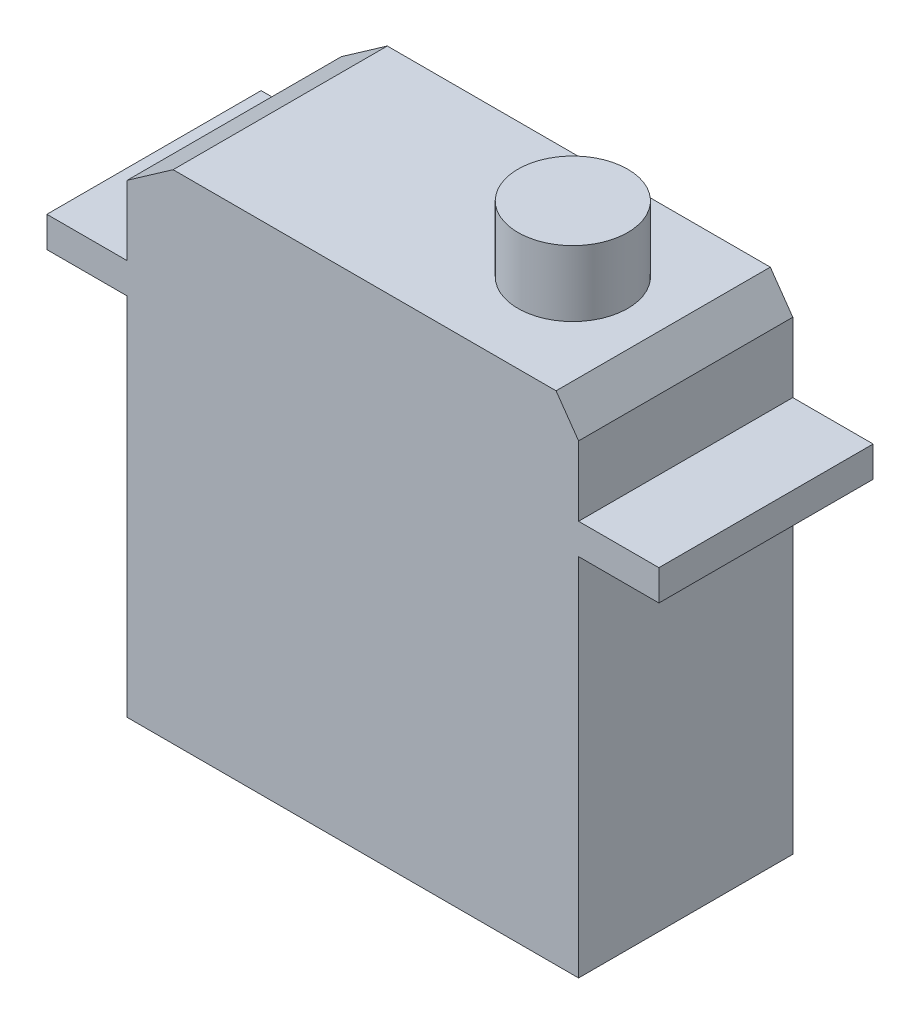
SolidWorks part; units mm, degrees
ref_plane "XY" through (0, 0, 0) normal (0, 0, 1) x (1, 0, 0)
ref_plane "XZ" through (0, 0, 0) normal (0, 1, 0) x (1, 0, 0)
ref_plane "YZ" through (0, 0, 0) normal (1, 0, 0) x (0, 0, -1)
ref_axis "X" through (-88.99, 0, 0) along (1, 0, 0)
ref_axis "Y" through (0, -55, 0) along (0, 1, 0)
ref_axis "Z" through (0, 0, 55) along (0, 0, -1)
sketch "Sketch1" plane through (0, 0, 0) normal (0, 0, 1) x (1, 0, 0)
  line L0 (-14.75, 11.925) -> (-20, 11.925)
  line L1 (-14.75, -11.925) -> (14.75, -11.925)
  line L2 (-14.75, -11.925) -> (-14.75, 11.925)
  line L4 (14.75, -11.925) -> (14.75, 11.925)
  line L5 (-14.75, -11.925) -> (14.75, 11.925) construction
  line L6 (-14.75, 11.925) -> (14.75, -11.925) construction
  line L7 (-20, 11.925) -> (-20, 13.925)
  line L8 (-20, 13.925) -> (-14.75, 13.925)
  line L9 (-14.75, 13.925) -> (-14.75, 18.4744)
  line L10 (-14.75, 18.4744) -> (-11.75, 20.575)
  line L11 (-11.75, 20.575) -> (13.2791, 20.575)
  line L12 (13.2791, 20.575) -> (14.75, 18.4744)
  line L13 (14.75, 18.4744) -> (14.75, 13.925)
  line L14 (14.75, 13.925) -> (20, 13.925)
  line L15 (20, 13.925) -> (20, 11.925)
  line L16 (20, 11.925) -> (14.75, 11.925)
  point P0 (0, 0)
  point P6 (14.5973, -11.8031)
  point P17 (14.75, 18.4744)
  point P18 (0, 0)
  dimension "D1" = 23.85
  dimension "D2" = 29.5
  dimension "D3" = 8.65
  dimension "D4" = 40
  dimension "D5" = 2
  dimension "D6" = 125
  dimension "D7" = 3
extrude "Boss-Extrude1" add sketch "Sketch1" along normal mid plane 14
sketch "Sketch2" plane through (0, 20.575, 0) normal (0, 1, 0) x (1, 0, 0)
  line L0 (0, 0) -> (14.75, 0) construction
  line L1 (14.75, -7) -> (14.75, 7) construction
  circle A0 centre (7.375, 0) radius 3.5871
extrude "Boss-Extrude2" add sketch "Sketch2" along normal blind 4.3
